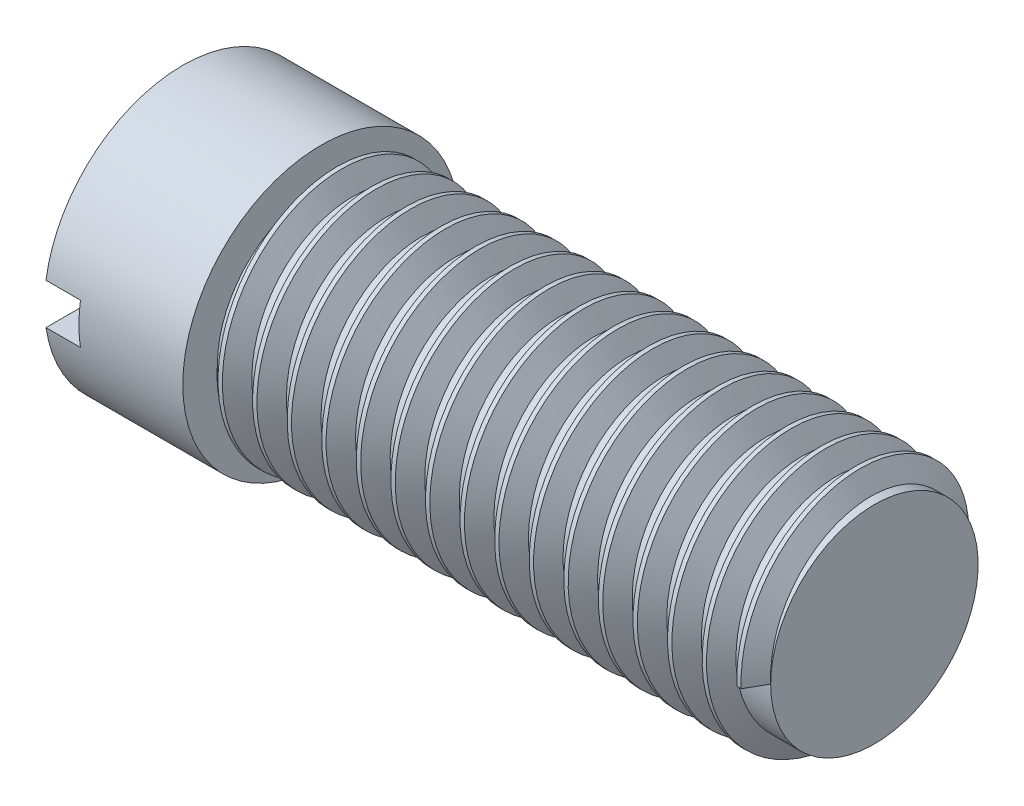
SolidWorks part; units mm, degrees
ref_plane "Front Plane" through (0, 0, 0) normal (0, 0, 1) x (1, 0, 0)
ref_plane "Top Plane" through (0, 0, 0) normal (0, 1, 0) x (1, 0, 0)
ref_plane "Right Plane" through (0, 0, 0) normal (1, 0, 0) x (0, 0, -1)
sketch "Sketch1" plane through (0, 0, 0) normal (0, 0, 1) x (1, 0, 0)
  line L0 (-5, 0) -> (5, 0)
  line L1 (-5, 0) -> (-5, 2)
  line L2 (-5, 2) -> (-3, 2)
  line L3 (-3, 2) -> (-3, 1.5)
  line L4 (-3, 1.5) -> (5, 1.5)
  line L5 (5, 1.5) -> (5, 0)
  point P3 (0, 0)
  dimension "D1" = 10
  dimension "D2" = 2
  dimension "D3" = 1.5
revolve "Revolve1" add sketch "Sketch1" angle 360 about L0
sketch "Sketch2" plane through (0, 0, 0) normal (0, 0, 1) x (1, 0, 0)
  line L0 (-5, 2) -> (-5, -2) construction
  line L2 (-5.4986, 0.2959) -> (-4.5014, 0.2959)
  line L3 (-5.4986, 0.2959) -> (-5.4986, -0.2959)
  line L4 (-5.4986, -0.2959) -> (-4.5014, -0.2959)
  line L5 (-4.5014, 0.2959) -> (-4.5014, -0.2959)
  line L6 (-5.4986, 0.2959) -> (-4.5014, -0.2959) construction
  line L7 (-5.4986, -0.2959) -> (-4.5014, 0.2959) construction
  point P1 (-5, 0)
  point P7 (0, 0)
  dimension "D1" = 4.5014
  dimension "D2" = 0.2959
extrude "Cut-Extrude1" cut sketch "Sketch2" against normal through all both and the other way through all
thread "Thread2" pitch 0.5 method extrude profile "Thread Profile2" start angle 0, offset 0, length 8, pitch 0.5, diameter 3
ref_plane "Plane2" through (5, 0, 1.5) normal (0, -1, 0) x (0, 0, 1)
sketch "Thread Profile2" plane through (5, 0, 1.5) normal (0, -1, 0) x (0, 0, 1)
  line L0 (0, 0) -> (0, 0.5) construction
  line L1 (0, 0) -> (0.2706, 0.1562)
  line L2 (0.2706, 0.1562) -> (0.2706, 0.2187)
  line L3 (0.2706, 0.2187) -> (0, 0.375)
  line L4 (0.2706, 0.1875) -> (0, 0.1875) construction
  line L11 (0, 0) -> (0, 0.375)
  point P2 (0, 0)
  dimension "Pitch" = 0.5
  dimension "Profile_Angle" = 60
  dimension "Profile_Land" = 0.0625
  dimension "Profile_Height" = 0.2706
